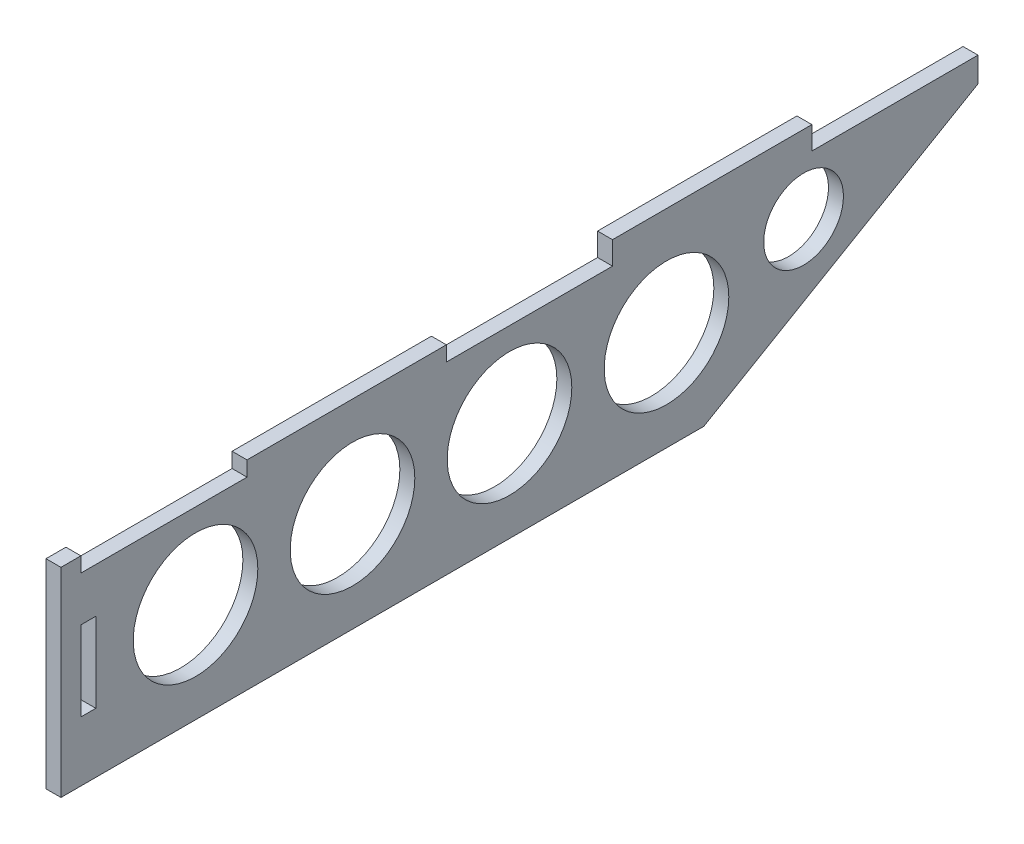
SolidWorks part; units mm, degrees
ref_plane "Front Plane" through (0, 0, 0) normal (0, 0, 1) x (1, 0, 0)
ref_plane "Top Plane" through (0, 0, 0) normal (0, 1, 0) x (1, 0, 0)
ref_plane "Right Plane" through (0, 0, 0) normal (1, 0, 0) x (0, 0, -1)
sketch "Sketch1" plane through (0, 0, 0) normal (1, 0, 0) x (0, 0, -1)
  line L0 (180, -8) -> (125, -40)
  line L1 (0, 0) -> (180, 0)
  line L2 (0, 0) -> (0, -40) construction
  line L3 (0, -40) -> (125, -40)
  line L4 (180, 0) -> (180, -8)
  line L5 (125, -40) -> (180, -40) construction
  line L6 (180, -8) -> (180, -40) construction
  line L7 (0, -20) -> (180, -20) construction
  line L8 (0, 0) -> (33.3333, 0)
  line L9 (0, 0) -> (0, -3)
  line L10 (0, -3) -> (33.3333, -3)
  line L11 (33.3333, 0) -> (33.3333, -3)
  line L12 (73.3333, 0) -> (106.6667, 0)
  line L13 (73.3333, 0) -> (73.3333, -3)
  line L14 (73.3333, -3) -> (106.6667, -3)
  line L15 (106.6667, 0) -> (106.6667, -3)
  line L16 (146.6667, 0) -> (180, 0)
  line L17 (146.6667, 0) -> (146.6667, -3)
  line L18 (146.6667, -3) -> (180, -3)
  line L19 (180, 0) -> (180, -3)
  line L20 (0, -12) -> (3, -12)
  line L21 (0, -12) -> (0, -28)
  line L22 (0, -28) -> (3, -28)
  line L23 (3, -12) -> (3, -28)
  line L24 (0, -40) -> (-4, -40)
  line L25 (-4, -40) -> (-4, 0)
  line L26 (-4, 0) -> (0, 0)
  circle A0 centre (23, -20) radius 12.5
  circle A1 centre (54.5, -20) radius 12.5
  circle A2 centre (86, -20) radius 12.5
  circle A3 centre (117.5, -20) radius 12.5
  circle A4 centre (145, -14) radius 8
  dimension "D12" = 25
  dimension "D13" = 16
  dimension "D1" = 40
  dimension "D2" = 180
  dimension "D3" = 8
  dimension "D4" = 125
  dimension "D5" = 3
  dimension "D10" = 9
  dimension "D11" = 16
  dimension "D14" = 145
  dimension "D15" = 14
  dimension "D16" = 23
  dimension "D17" = 31.5
  dimension "D18" = 31.5
  dimension "D19" = 31.5
  dimension "D7" = 40
  dimension "D6" = 40
  dimension "D8" = 4
extrude "Boss-Extrude1" add sketch "Sketch1" along normal blind 3 contours L20 L23 L22 L2 L3 L0 L4 L18 L17 L1 L15 L14 L13 L11 L10 A4 A3 A2 A1 A0 region at (0, -22.3725, -151.5531)
sketch "Sketch2" plane through (3, 0, 0) normal (1, 0, 0) x (0, 0, -1)
  line L0 (146.6667, 0) -> (146.6667, -3) construction
  line L1 (106.6667, 0) -> (146.6667, 0)
  line L2 (106.6667, 0) -> (106.6667, 1.6)
  line L3 (106.6667, 1.6) -> (146.6667, 1.6)
  line L4 (146.6667, 0) -> (146.6667, 1.6)
  dimension "D1" = 1.6
extrude "Boss-Extrude2" add sketch "Sketch2" against normal blind 3
equation "\"D18@Sketch1\"=\"D19@Sketch1\""
equation "\"D17@Sketch1\"=\"D19@Sketch1\""
